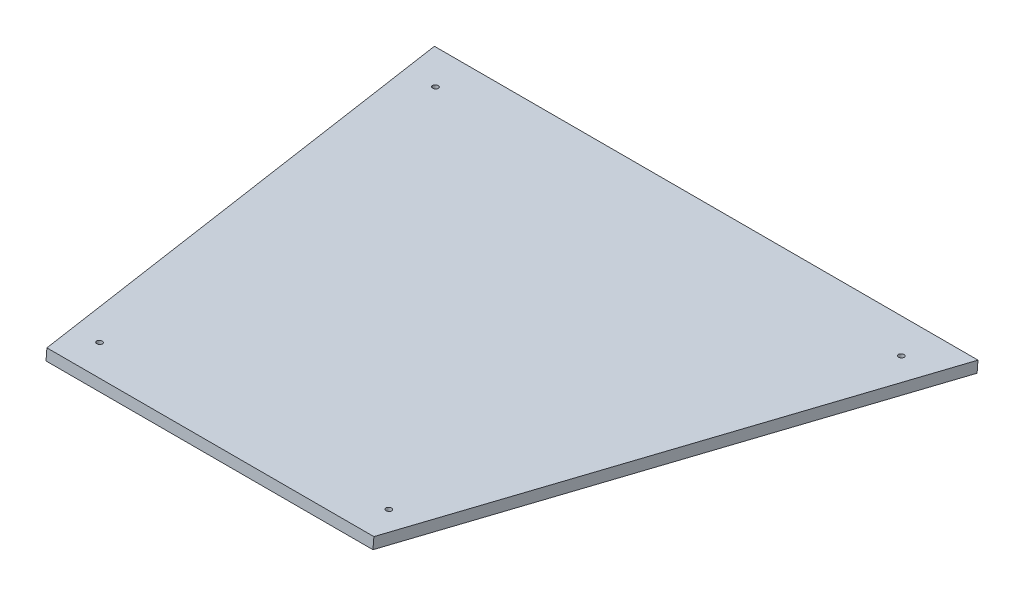
SolidWorks part; units mm, degrees
ref_plane "Front Plane" through (0, 0, 0) normal (0, 0, 1) x (1, 0, 0)
ref_plane "Top Plane" through (0, 0, 0) normal (0, 1, 0) x (1, 0, 0)
ref_plane "Right Plane" through (0, 0, 0) normal (1, 0, 0) x (0, 0, -1)
ref_plane "Plane1" through (-0.0008, -10027.3097, 827.1875) normal (0, -0.9966, 0.0822) x (-1, 0, 0)
sketch "Sketch1" plane through (-0.0008, -10027.3097, 827.1875) normal (0, -0.9966, 0.0822) x (-1, 0, 0)
  line L0 (927.9324, -1893.2884) -> (1306.8393, -1893.2884)
  line L1 (1306.8393, -1893.2884) -> (1432.3521, -1316.7398)
  line L2 (1432.3521, -1316.7398) -> (802.4196, -1316.7398)
  line L3 (802.4196, -1316.7398) -> (927.9324, -1893.2884)
  line L4 (802.4183, -1316.7398) -> (1432.3534, -1316.7398) construction
  line L5 (928.076, -1893.948) -> (801.0629, -1310.5075) construction
  line L6 (1433.7088, -1310.5075) -> (1306.6957, -1893.948) construction
  line L7 (1306.8419, -1893.2884) -> (927.9298, -1893.2884) construction
extrude "Boss-Extrude1" add sketch "Sketch1" along normal blind 12.7
sketch "Sketch2" plane through (-0.0008, -10027.3097, 827.1875) normal (0, 0.9966, -0.0822) x (1, 0, 0)
  line L0 (-927.9324, -1893.2884) -> (-1306.8393, -1893.2884) construction
  line L1 (-1306.8393, -1893.2884) -> (-1432.3521, -1316.7398) construction
  line L2 (-802.4196, -1316.7398) -> (-927.9324, -1893.2884) construction
  line L3 (-1432.3521, -1316.7398) -> (-802.4196, -1316.7398) construction
  circle A0 centre (-1284.9566, -1854.0196) radius 3.175
  circle A3 centre (-949.7975, -1853.9387) radius 3.175
  circle A4 centre (-1387.3011, -1360.7012) radius 3.175
  circle A6 centre (-847.4706, -1360.7012) radius 3.175
  dimension "D1" = 6.35
  dimension "D2" = 39.2688
  dimension "D3" = 29.735
  dimension "D4" = 6.35
  dimension "D5" = 39.3497
  dimension "D7" = 6.35
  dimension "D10" = 6.35
  dimension "D6" = 29.735
  dimension "D8" = 43.9614
  dimension "D9" = 34.6688
  dimension "D11" = 34.6688
  dimension "D12" = 43.9614
extrude "Cut-Extrude1" cut sketch "Sketch2" against normal through all
